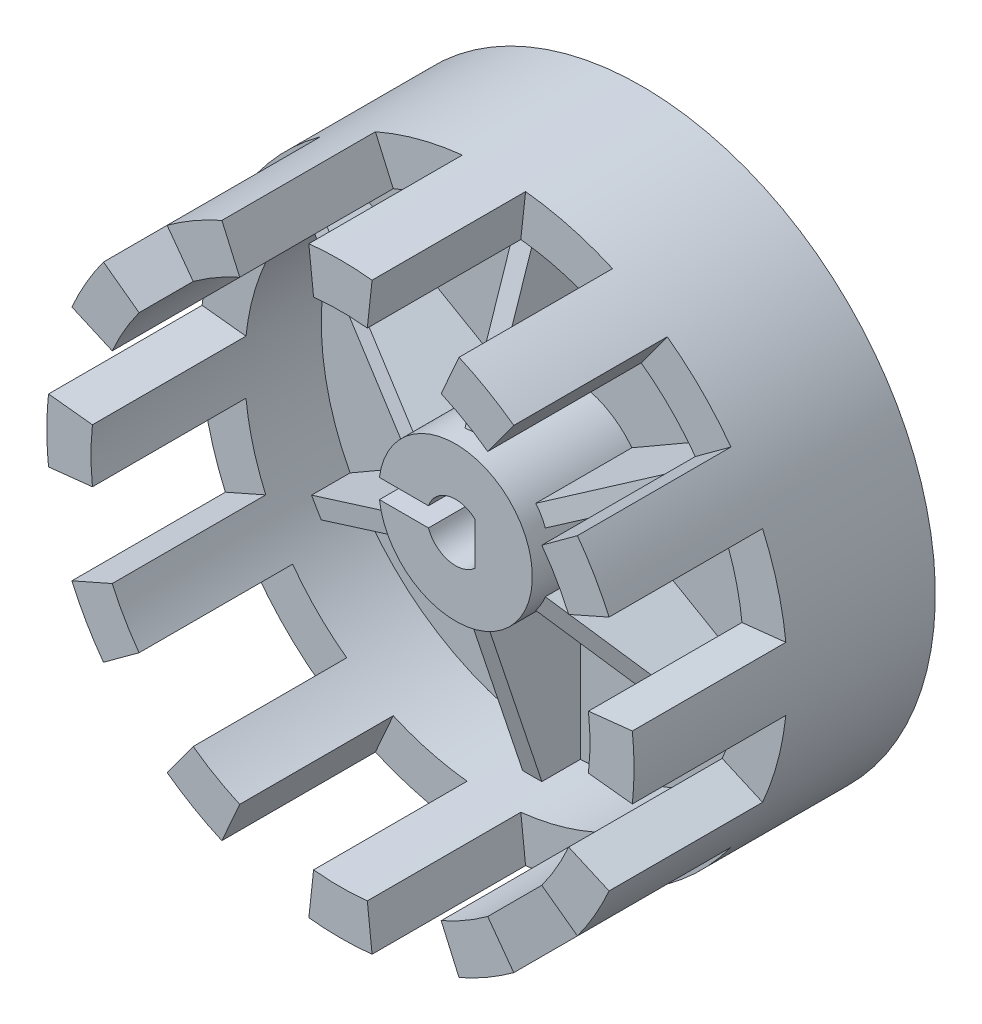
SolidWorks part; units mm, degrees
ref_plane "Plan de face" through (0, 0, 0) normal (0, 0, 1) x (1, 0, 0)
ref_plane "Plan de dessus" through (0, 0, 0) normal (0, 1, 0) x (1, 0, 0)
ref_plane "Plan de droite" through (0, 0, 0) normal (1, 0, 0) x (0, 0, -1)
sketch "Esquisse1" plane through (0, 0, 0) normal (0, 0, 1) x (1, 0, 0)
  circle A0 centre (0, 0) radius 15.3
  dimension "D1" = 30.6
extrude "Boss.-Extru.1" add sketch "Esquisse1" along normal blind 3.5
sketch "Esquisse7" plane through (0, 0, 0) normal (0, 0, -1) x (-1, 0, 0)
  circle A0 centre (0, 0) radius 3.5
  circle A1 centre (0, 0) radius 11
  circle A2 centre (0, 0) radius 15.3 construction
  circle A3 centre (0, 0) radius 15.3
  circle M2 centre (0, 0) radius 15.3
  dimension "D1" = 7
  dimension "D2" = 22
extrude "Boss.-Extru.10" add sketch "Esquisse7" along normal mid plane 0.4 contours A1 M2 | A0 region at (0, 0, 0) region at (14.8673, 0, 0)
sketch "Esquisse2" plane through (0, 0, 3.5) normal (0, 0, 1) x (1, 0, 0)
  circle A0 centre (0, 0) radius 4
  dimension "D1" = 8
extrude "Boss.-Extru.2" add sketch "Esquisse2" along normal blind 6
sketch "Esquisse3" plane through (0, 0, 0) normal (0, 0, 1) x (1, 0, 0)
  line L0 (1, 1.118) -> (1, -1.118)
  line L1 (-1.4142, 0.5) -> (-8.4142, 0.5)
  line L2 (-8.4142, 0.5) -> (-8.4142, -0.5)
  line L3 (-8.4142, -0.5) -> (-1.4142, -0.5)
  arc A0 (1, 1.118) -> (1, -1.118) centre (0, 0) ccw construction
  arc A1 (-1.4142, 0.5) -> (1, 1.118) centre (0, 0) cw
  arc A2 (-1.4142, -0.5) -> (1, -1.118) centre (0, 0) ccw
  point P1 (-1.5, 0)
  point P9 (-8.4142, 0)
  dimension "D1" = 3
  dimension "D4" = 1
  dimension "D2" = 2.5
  dimension "D3" = 7
extrude "Enlèv. mat.-Extru.2" cut sketch "Esquisse3" along normal through all both and the other way through all
sketch "Esquisse4" plane through (0, 0, 3.5) normal (0, 0, 1) x (1, 0, 0)
  circle A0 centre (0, 0) radius 13
  circle A1 centre (0, 0) radius 15.3 construction
  circle A2 centre (0, 0) radius 15.3
  point P6 (0, 13)
  point P7 (0, 15.3)
  dimension "D1" = 2.3
extrude "Boss.-Extru.3" add sketch "Esquisse4" along normal blind 4
sketch "Esquisse5" plane through (0, 0, 7.5) normal (0, 0, 1) x (1, 0, 0)
  line L0 (0, 0) -> (0, 15.3) construction
  line L1 (-1.6477, 15.211) -> (-1.4, 12.9244)
  line L2 (1.6477, 15.211) -> (1.4, 12.9244)
  circle A0 centre (0, 0) radius 15.3 construction
  arc A1 (-1.6477, 15.211) -> (1.6477, 15.211) centre (0, 0) cw
  arc A2 (-1.4, 12.9244) -> (1.4, 12.9244) centre (0, 0) cw
  circle A3 centre (0, 0) radius 13 construction
  point P12 (0, 0)
  point P13 (0, 15.3)
  point P14 (0, 0)
  dimension "D1" = 2.8
extrude "Boss.-Extru.4" add sketch "Esquisse5" along normal blind 8
ref_axis "Axe1" through (0, 0, -0.775) along (0, 0, 1)
pattern_circular "Répétition circulaire1" count 12 over 360 about axis through (0, 0, -0.775) along (0, 0, 1) of "Boss.-Extru.4"
ref_plane "Plan1" through (0, 0, 0) normal (1, 0, 0) x (0, 0, 1)
sketch "Esquisse6" plane through (0, 0, 0) normal (1, 0, 0) x (0, 0, 1)
  line L0 (8.8333, 3) -> (5.5, 13)
  line L2 (5.5, 13) -> (3.5, 13)
  line L3 (3.5, 13) -> (3.5, 3)
  line L4 (3.5, 3) -> (8.8333, 3)
  line L5 (3.5, -13) -> (3.5, 13) construction
  line L7 (9.5, 4) -> (3.5, 4) construction
  line L8 (15.5, 10.4929) -> (15.5, 11.8929) construction
  point P2 (0, 0)
  point P3 (8.5, 4)
  point P10 (5.5392, 12.115)
  point P11 (0, 0)
  point P14 (0, 0)
  point P16 (3.5, 12.6715)
  point P17 (0, 0)
  point P19 (0, 0)
  dimension "D1" = 1
  dimension "D2" = 10
  dimension "D3" = 1
extrude "Boss.-Extru.9" add sketch "Esquisse6" along normal mid plane 1 contours L0 L2 L3 L4
pattern_circular "Répétition circulaire4" count 6 over 360 about axis through (0, 0, -0.775) along (0, 0, 1) of "Boss.-Extru.9"
